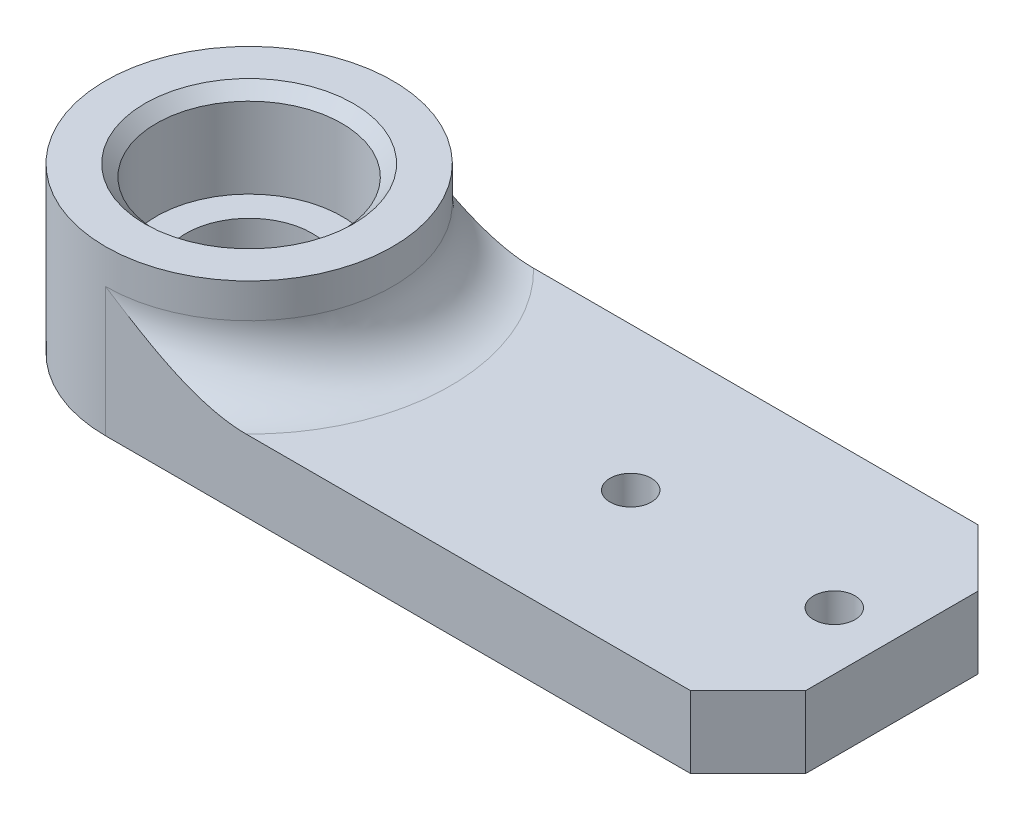
SolidWorks part; units mm, degrees
material "PLA"
ref_plane "Front Plane" through (0, 0, 0) normal (0, 0, 1) x (1, 0, 0)
ref_plane "Top Plane" through (0, 0, 0) normal (0, 1, 0) x (1, 0, 0)
ref_plane "Right Plane" through (0, 0, 0) normal (1, 0, 0) x (0, 0, -1)
sketch "Sketch1" plane through (0, 0, 0) normal (0, 1, 0) x (1, 0, 0)
  circle A0 centre (0, 0) radius 4.1021
  circle A1 centre (0, 0) radius 6.35
  dimension "D1" = 8.2042
  dimension "D2" = 12.7
extrude "Bearing-Housing" add sketch "Sketch1" along normal blind 4.064
sketch "Sketch2" plane through (0, 0, 0) normal (0, -1, 0) x (1, 0, 0)
  circle A0 centre (0, 0) radius 6.35 construction
  circle A1 centre (0, 0) radius 6.35
  circle A2 centre (0, 0) radius 2.794
  dimension "D1" = 5.588
extrude "Cap" add sketch "Sketch2" along normal blind 3.175
sketch "Sketch3" plane through (0, -3.175, 0) normal (0, 1, 0) x (1, 0, 0)
  line L0 (0, 6.35) -> (28.4023, 6.35)
  line L1 (28.4023, 6.35) -> (28.4023, -6.35)
  line L2 (28.4023, -6.35) -> (0, -6.35)
  line L3 (0, 0) -> (28.4023, 0) construction
  line L4 (28.4023, 0) -> (32.8625, 0) construction
  circle A0 centre (0, 0) radius 6.35 construction
  arc A2 (0, -6.35) -> (0, 6.35) centre (0, 0) ccw
  circle A3 centre (25.8623, 0) radius 0.9144
  circle A4 centre (16.8631, 0) radius 0.9144
  dimension "D4" = 1.8288
  dimension "D5" = 1.8288
  dimension "D1" = 32.8625
  dimension "D2" = 2.54
  dimension "D3" = 8.9992
  dimension "D6" = 4.4602
extrude "Extender" add sketch "Sketch3" along normal blind 3.175
fillet "Fillet1" radius 2.54 1 edges at (6.35, 0, 0)
chamfer "Chamfer1" distance 0.508 angle 45 1 edges at (0, 4.064, 4.1021)
chamfer "Chamfer2" distance 2.54 angle 45 2 edges at (28.4023, -1.5875, 6.35) (28.4023, -1.5875, -6.35)
